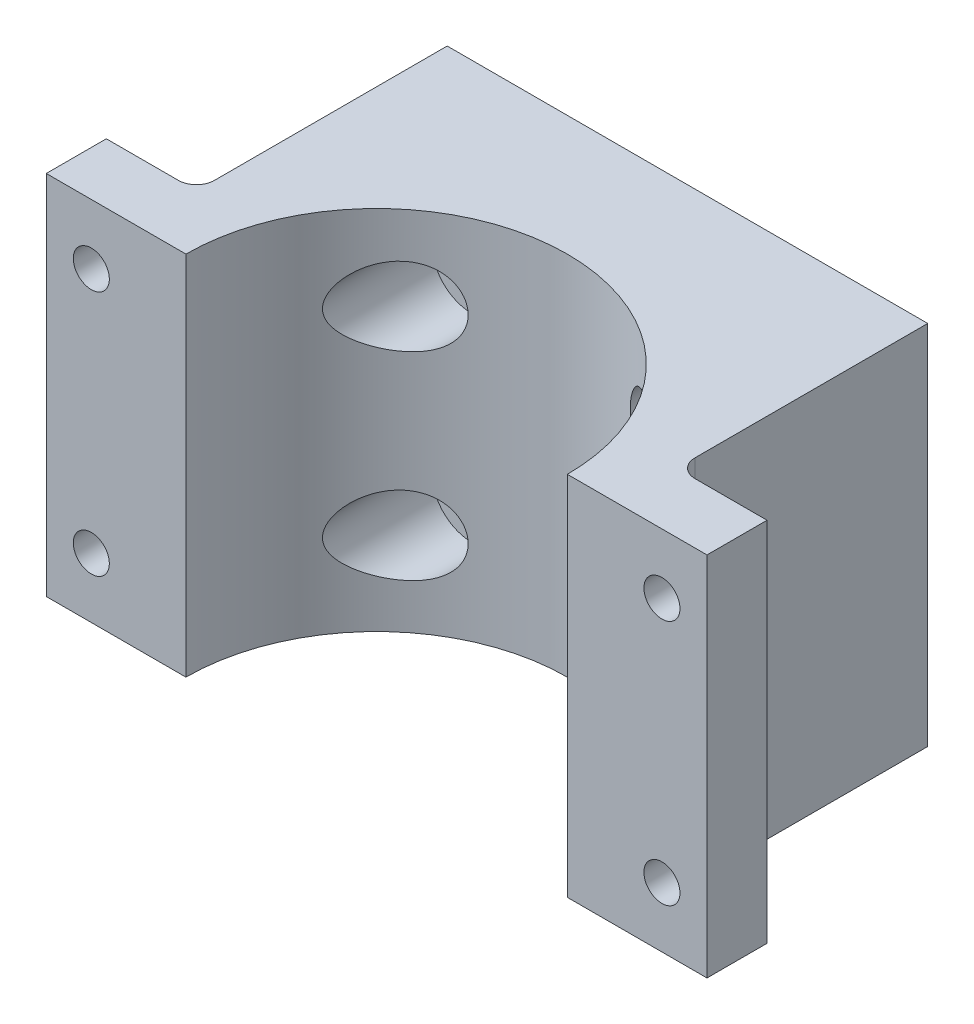
SolidWorks part; units mm, degrees
ref_plane "Front Plane" through (0, 0, 0) normal (0, 0, 1) x (1, 0, 0)
ref_plane "Top Plane" through (0, 0, 0) normal (0, 1, 0) x (1, 0, 0)
ref_plane "Right Plane" through (0, 0, 0) normal (1, 0, 0) x (0, 0, -1)
sketch "Sketch1" plane through (0, 0, 0) normal (0, 1, 0) x (1, 0, 0)
  line L0 (0, 0) -> (-40, 0)
  line L1 (-40, 0) -> (-40, -20)
  line L2 (0, 0) -> (40, 0)
  line L3 (40, 0) -> (40, -20)
  line L4 (-40, 0) -> (-40, -41.75)
  line L5 (-40, -51.75) -> (0, -51.75) construction
  line L6 (0, -51.75) -> (0, -20) construction
  line L7 (40, -20) -> (40, -41.75)
  line L8 (40, -51.75) -> (31.75, -51.75)
  line L9 (-40, -51.75) -> (-31.75, -51.75)
  line L10 (-40, -51.75) -> (-55, -51.75)
  line L11 (-55, -51.75) -> (-55, -41.75)
  line L12 (-55, -41.75) -> (-40, -41.75)
  line L13 (40, -51.75) -> (55, -51.75)
  line L14 (55, -51.75) -> (55, -41.75)
  line L15 (55, -41.75) -> (40, -41.75)
  arc A0 (31.75, -51.75) -> (-31.75, -51.75) centre (0, -51.75) ccw construction
  arc A1 (31.75, -51.75) -> (-31.75, -51.75) centre (0, -51.75) ccw
  dimension "D1" = 20
  dimension "D2" = 40
  dimension "D3" = 40
  dimension "D4" = 31.75
  dimension "D5" = 31.75
  dimension "D6" = 15
  dimension "D7" = 10
  dimension "D8" = 31.75
extrude "Boss-Extrude1" add sketch "Sketch1" along normal blind 61 contours A1 L8 L13 L14 L15 L7 L3 L2 L0 L1 L4 L12 L11 L10 L9 region at (20, 0, 1.2157)
sketch "Sketch2" plane through (0, 0, 41.75) normal (0, 0, -1) x (-1, 0, 0)
  line L0 (0, 61) -> (0, 0) construction
  line L1 (40, 61) -> (-40, 61) construction
  line L2 (-55, 61) -> (-55, 0) construction
  line L3 (-55, 61) -> (-40, 61) construction
  line L4 (-55, 0) -> (-40, 0) construction
  circle A0 centre (-47.5, 51) radius 3
  circle A1 centre (-47.5, 10) radius 3
  circle A2 centre (47.5, 10) radius 3
  circle A3 centre (47.5, 51) radius 3
  dimension "D2" = 6
  dimension "D1" = 7.5
  dimension "D3" = 10
  dimension "D4" = 10
extrude "Cut-Extrude1" cut sketch "Sketch2" against normal through all
sketch "Sketch3" plane through (0, 0, 0) normal (0, 0, -1) x (-1, 0, 0)
  line L0 (0, 61) -> (0, 0) construction
  line L1 (40, 61) -> (-40, 61) construction
  line L2 (-40, 61) -> (-40, 0) construction
  line L3 (40, 0) -> (-40, 0) construction
  circle A0 centre (-20, 47) radius 4
  circle A1 centre (-20, 14) radius 4
  circle A2 centre (20, 14) radius 4
  circle A3 centre (20, 47) radius 4
  circle A4 centre (-20, 47) radius 6.5
  circle A5 centre (-20, 14) radius 6.5
  circle A6 centre (20, 14) radius 6.5
  circle A7 centre (20, 47) radius 6.5
  dimension "D1" = 8
  dimension "D5" = 13
  dimension "D2" = 20
  dimension "D3" = 14
  dimension "D4" = 14
extrude "Cut-Extrude2" cut sketch "Sketch3" against normal through all contours A0 | A1 | A2 | A3 region at (20, 47, 0) region at (20, 14, 0) region at (-20, 14, 0) region at (-20, 47, 0)
extrude "Cut-Extrude3" cut sketch "Sketch3<4>" against normal blind 61 from offset 16 offset against normal yes
sketch "Sketch3<4>" plane through (0, 0, 0) normal (0, 0, -1) x (-1, 0, 0) same geometry as "Sketch3"
fillet "Fillet1" radius 3 2 edges at (40, 30.5, 41.75) (-40, 30.5, 41.75)
